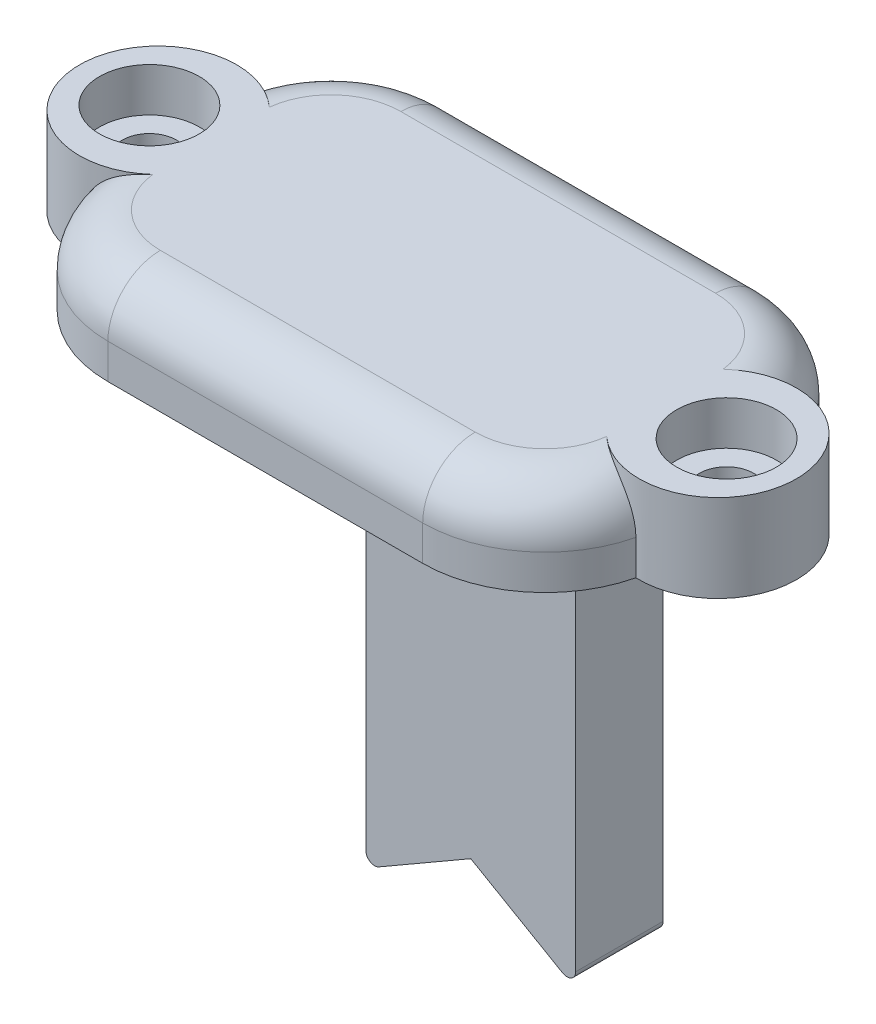
SolidWorks part; units mm, degrees
ref_plane "Alzado" through (0, 0, 0) normal (0, 0, 1) x (1, 0, 0)
ref_plane "Planta" through (0, 0, 0) normal (0, 1, 0) x (1, 0, 0)
ref_plane "Vista lateral" through (0, 0, 0) normal (1, 0, 0) x (0, 0, -1)
sketch "Croquis1" plane through (0, 0, 0) normal (0, 1, 0) x (1, 0, 0)
  line L0 (-4.5, 9.875) -> (36.5, 9.875) construction
  line L1 (7, 0) -> (25, 0)
  line L2 (0, 7) -> (0, 12.75) construction
  line L3 (7, 19.75) -> (25, 19.75)
  line L4 (32, 7) -> (32, 12.75) construction
  line L5 (16, 19.75) -> (16, 0) construction
  arc A0 (0, 7) -> (7, 0) centre (7, 7) ccw
  arc A1 (25, 0) -> (32, 7) centre (25, 7) ccw
  arc A2 (32, 12.75) -> (25, 19.75) centre (25, 12.75) ccw
  arc A3 (7, 19.75) -> (0, 12.75) centre (7, 12.75) ccw
  arc A4 (0.1903, 14.371) -> (0.1903, 5.379) centre (0, 9.875) ccw
  arc A5 (31.8097, 5.379) -> (31.8097, 14.371) centre (32, 9.875) ccw
  circle A6 centre (-0.5, 9.875) radius 1.55
  circle A7 centre (32.5, 9.875) radius 1.55
  point P7 (0, 0)
  point P10 (32, 0)
  point P13 (32, 19.75)
  point P16 (0, 19.75)
  point P24 (-0.5, 9.875)
  dimension "D3" = 7
  dimension "D4" = 9
  dimension "D5" = 0.5
  dimension "D6" = 3.1
  dimension "D1" = 19.75
  dimension "D2" = 32
extrude "Saliente-Extruir2" add sketch "Croquis1" along normal blind 5 contours A5 A2 L3 A3 A4 A0 L1 A1 region at (16, 0, -9.875)
sketch "Croquis2" plane through (0, 5, 0) normal (0, 1, 0) x (1, 0, 0)
  circle A0 centre (-0.5, 9.875) radius 2.85
  circle A1 centre (32.5, 9.875) radius 2.85
  dimension "D1" = 5.7
extrude "Cortar-Extruir1" cut sketch "Croquis2" against normal blind 2.5
fillet "Redondeo2" radius 3 6 edges at (2.661, 5, -18.243) (29.339, 5, -18.243) (2.661, 5, -1.507) (29.339, 5, -1.507) (16, 5, -19.75) (16, 5, 0)
sketch "Sketch1" plane through (0, 0, 0) normal (0, -1, 0) x (1, 0, 0)
  line L0 (16, -19.75) -> (16, 0) construction
  line L1 (7, -19.75) -> (25, -19.75) construction
  line L2 (7, 0) -> (25, 0) construction
  line L3 (21.5303, -14.25) -> (11.4001, -14.25) construction
  line L5 (22, -16.75) -> (10, -16.75)
  line L6 (22, -16.75) -> (22, -11.75)
  line L7 (22, -11.75) -> (10, -11.75)
  line L8 (10, -16.75) -> (10, -11.75)
  line L9 (22, -16.75) -> (10, -11.75) construction
  line L10 (22, -11.75) -> (10, -16.75) construction
  point P8 (16, -14.25)
  point P9 (16, -14.25)
  dimension "D1" = 5.5
  dimension "D2" = 12
  dimension "D3" = 5
extrude "Boss-Extrude1" add sketch "Sketch1" along normal blind 28.5
sketch "Sketch2" plane through (0, 0, -11.75) normal (0, 0, 1) x (1, 0, 0)
  line L0 (16, 0) -> (16, -28.5) construction
  line L1 (7, 0) -> (25, 0) construction
  line L2 (22, -28.5) -> (10, -28.5) construction
  line L3 (22, 0) -> (10, 0) construction
  line L4 (16, -25) -> (9.9378, -28.5)
  line L5 (16, -25) -> (22.0622, -28.5)
  line L6 (22.0622, -28.5) -> (9.9378, -28.5)
  point P6 (16, -25)
  dimension "D1" = 25
  dimension "D2" = 7
  dimension "D3" = 7
  dimension "D4" = 3.5
extrude "Cut-Extrude1" cut sketch "Sketch2" against normal up to surface (5 mm away) up to face at (16, -14.25, -16.75)
fillet "Fillet1" radius 0.5 2 edges at (10, -28.4641, -14.25) (22, -28.4641, -14.25)
